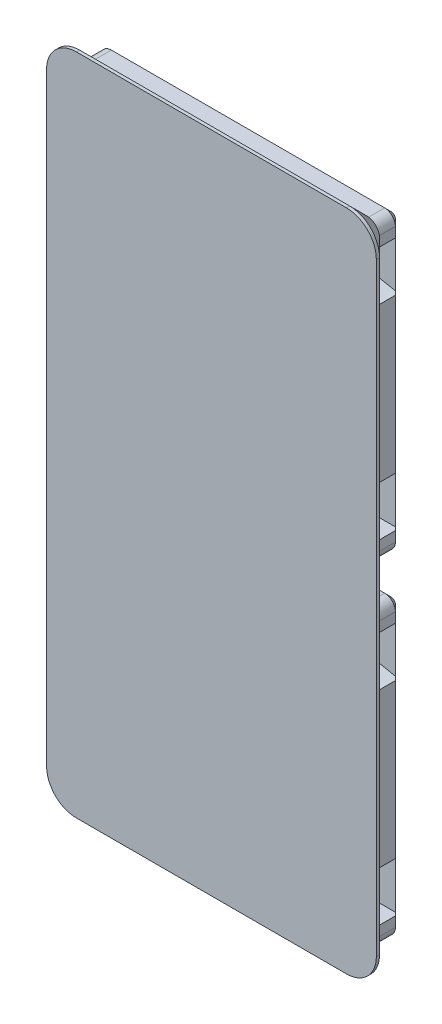
SolidWorks part; units mm, degrees
ref_plane "Front Plane" through (0, 0, 0) normal (0, 0, 1) x (1, 0, 0)
ref_plane "Top Plane" through (0, 0, 0) normal (0, 1, 0) x (1, 0, 0)
ref_plane "Right Plane" through (0, 0, 0) normal (1, 0, 0) x (0, 0, -1)
sketch "Sketch1" plane through (0, 0, 0) normal (0, 0, 1) x (1, 0, 0)
  line L1 (18.55, 18.55) -> (-18.55, 18.55)
  line L2 (18.55, 18.55) -> (18.55, -18.55)
  line L3 (18.55, -18.55) -> (-18.55, -18.55)
  line L4 (-18.55, 18.55) -> (-18.55, -18.55)
  line L5 (18.55, 18.55) -> (-18.55, -18.55) construction
  line L6 (18.55, -18.55) -> (-18.55, 18.55) construction
  point P0 (0, 0)
  dimension "D1" = 37.1
extrude "Boss-Extrude1" add sketch "Sketch1" along normal blind 2.6
sketch "Sketch2" plane through (0, 0, 2.6) normal (0, 0, 1) x (1, 0, 0)
  line L1 (-20.75, 20.75) -> (20.75, 20.75)
  line L2 (-20.75, 20.75) -> (-20.75, -20.75)
  line L3 (-20.75, -20.75) -> (20.75, -20.75)
  line L4 (20.75, 20.75) -> (20.75, -20.75)
  line L5 (-20.75, 20.75) -> (20.75, -20.75) construction
  line L6 (-20.75, -20.75) -> (20.75, 20.75) construction
  point P0 (0, 0)
  dimension "D1" = 41.5
extrude "Boss-Extrude2" add sketch "Sketch2" along normal blind 2.4
sketch "Sketch8" plane through (0, 0, 2.6) normal (0, 0, -1) x (-1, 0, 0)
  line L0 (-18.55, 18.55) -> (-18.55, 5.0094) construction
  line L1 (-18.55, -18.55) -> (-18.55, 18.55) construction
  line L2 (-14.9962, 10.4) -> (-18.55, 9.7)
  line L8 (12.7, 15.95) -> (-12.7, 15.95) construction
  line L9 (12.7, 9.45) -> (-12.7, 9.45) construction
  line L11 (-12.7, 15.95) -> (-18.55, 15.95)
  line L12 (-12.7, 12.7) -> (-12.7, -12.7)
  line L13 (-12.7, -12.7) -> (12.7, -12.7)
  line L14 (12.7, -12.7) -> (12.7, 12.7)
  line L15 (12.7, 12.7) -> (-12.7, 12.7)
  line L16 (-12.7, 9.45) -> (-12.7, -12.7) construction
  line L17 (-12.7, -12.7) -> (12.7, -12.7) construction
  line L18 (12.7, -12.7) -> (12.7, 12.7) construction
  line L19 (12.7, 12.7) -> (-12.7, 12.7) construction
  line L22 (-18.55, 15.95) -> (-18.55, 9.7)
  arc A0 (-12.7, 15.95) -> (-12.7, 9.45) centre (-12.7, 12.7) cw
  arc A1 (-12.7, 9.45) -> (-14.9962, 10.4) centre (-12.7, 12.7) cw
  dimension "D4" = 5.55
  dimension "D5" = 6.25
  dimension "D1" = 8.05
  dimension "D2" = 3.25
  dimension "D3" = 3.25
extrude "Base Magnet Slot" cut sketch "Sketch8" against normal blind 0.4 and the other way blind 2.2
fillet "Fillet1" radius 1.35 4 edges at (18.55, 18.55, 1.3) (18.55, -18.55, 1.3) (-18.55, -18.55, 1.3) (-18.55, 18.55, 1.3)
fillet "Fillet2" radius 3.75 4 edges at (20.75, -20.75, 3.8) (20.75, 20.75, 3.8) (-20.75, -20.75, 3.8) (-20.75, 20.75, 3.8)
chamfer "Chamfer1" distance 0.8 angle 45 8 edges at (-18.1546, 18.1546, 0) (-18.55, 0, 0) (-18.1546, -18.1546, 0) (0, -18.55, 0) (18.1546, -18.1546, 0) (18.55, 0, 0) (18.1546, 18.1546, 0) (0, 18.55, 0)
chamfer "Chamfer2" distance 2.4 angle 45 8 edges at (20.75, 0, 2.6) (19.6517, 19.6517, 2.6) (19.6517, -19.6517, 2.6) (0, 20.75, 2.6) (0, -20.75, 2.6) (-19.6517, 19.6517, 2.6) (-19.6517, -19.6517, 2.6) (-20.75, 0, 2.6)
mirror "Mirror1" about plane through (0, 0, 0) normal (0, 1, 0) of "Base Magnet Slot"
mirror "Mirror2" about plane through (0, 0, 0) normal (1, 0, 0) of "Mirror1"
sketch "Sketch14" plane through (0, 0, 0) normal (0, 0, -1) x (-1, 0, 0)
  line L0 (17.2, 17.75) -> (-17.2, 17.75) construction
  line L1 (-3, -15.75) -> (3, -15.75)
  line L2 (-3, -15.75) -> (-3, -3)
  line L3 (-3, 15.75) -> (3, 15.75)
  line L4 (3, -15.75) -> (3, -3)
  line L5 (-3, -15.75) -> (3, 15.75) construction
  line L6 (-3, 15.75) -> (3, -15.75) construction
  line L7 (-17.75, 17.2) -> (-17.75, -17.2) construction
  line L8 (-15.75, 3) -> (-3, 3)
  line L9 (-15.75, 3) -> (-15.75, -3)
  line L10 (-15.75, -3) -> (-3, -3)
  line L11 (15.75, 3) -> (15.75, -3)
  line L12 (-15.75, 3) -> (15.75, -3) construction
  line L13 (-15.75, -3) -> (15.75, 3) construction
  line L14 (-3, 3) -> (-3, 15.75)
  line L16 (3, 3) -> (15.75, 3)
  line L17 (3, 3) -> (3, 15.75)
  line L19 (3, -3) -> (15.75, -3)
  point P0 (0, 0)
  point P10 (0, 0)
  dimension "D1" = 6
  dimension "D2" = 2
  dimension "D3" = 2
extrude "Cut-Extrude2" cut sketch "Sketch14" against normal blind 3
fillet "Fillet4" radius 1 36 edges at (-9.375, -3, 0) (9.375, -3, 0) (-3, 9.375, 0) (-15.75, 0, 0) (0, -15.75, 0) (15.75, 0, 0) (0, 15.75, 0) (9.375, -3, 3) (-3, -9.375, 3) (-3, 9.375, 3) (3, 9.375, 3) (-9.375, 3, 0) (-3, -9.375, 0) (3, -9.375, 0) (9.375, 3, 0) (3, 9.375, 0) (0, -15.75, 3) (3, -9.375, 3) (3, -3, 1.5) (-15.75, 0, 3) (-9.375, -3, 3) (-9.375, 3, 3) (0, 15.75, 3) (9.375, 3, 3) (15.75, 0, 3) (-3, -3, 1.5) (-3, 3, 1.5) (3, 3, 1.5) (-15.75, 3, 1.5) (-15.75, -3, 1.5) (-3, -15.75, 1.5) (3, -15.75, 1.5) (15.75, -3, 1.5) (-3, 15.75, 1.5) (3, 15.75, 1.5) (15.75, 3, 1.5)
pattern_linear "LPattern1" count 2 spacing 42 along (0, -1, 0) of bodies 117
sketch "Sketch15" plane through (0, 0, 5) normal (0, 0, 1) x (1, 0, 0)
  line L0 (-17, -62.75) -> (17, -62.75) construction
  line L1 (20.75, -59) -> (20.75, -25) construction
  line L3 (-20.75, -25) -> (-20.75, -59) construction
  line L6 (17, 20.75) -> (-17, 20.75) construction
  line L8 (-17, -62.75) -> (17, -62.75)
  line L9 (20.75, -59) -> (20.75, 17)
  line L11 (-20.75, 17) -> (-20.75, -59)
  line L14 (17, 20.75) -> (-17, 20.75)
  arc A0 (17, -62.75) -> (20.75, -59) centre (17, -59) ccw construction
  arc A3 (-20.75, -59) -> (-17, -62.75) centre (-17, -59) ccw construction
  arc A5 (20.75, 17) -> (17, 20.75) centre (17, 17) ccw construction
  arc A6 (-17, 20.75) -> (-20.75, 17) centre (-17, 17) ccw construction
  arc A8 (17, -62.75) -> (20.75, -59) centre (17, -59) ccw
  arc A11 (-20.75, -59) -> (-17, -62.75) centre (-17, -59) ccw
  arc A13 (20.75, 17) -> (17, 20.75) centre (17, 17) ccw
  arc A14 (-17, 20.75) -> (-20.75, 17) centre (-17, 17) ccw
extrude "Boss-Extrude3" add sketch "Sketch15" along normal blind 0.4
